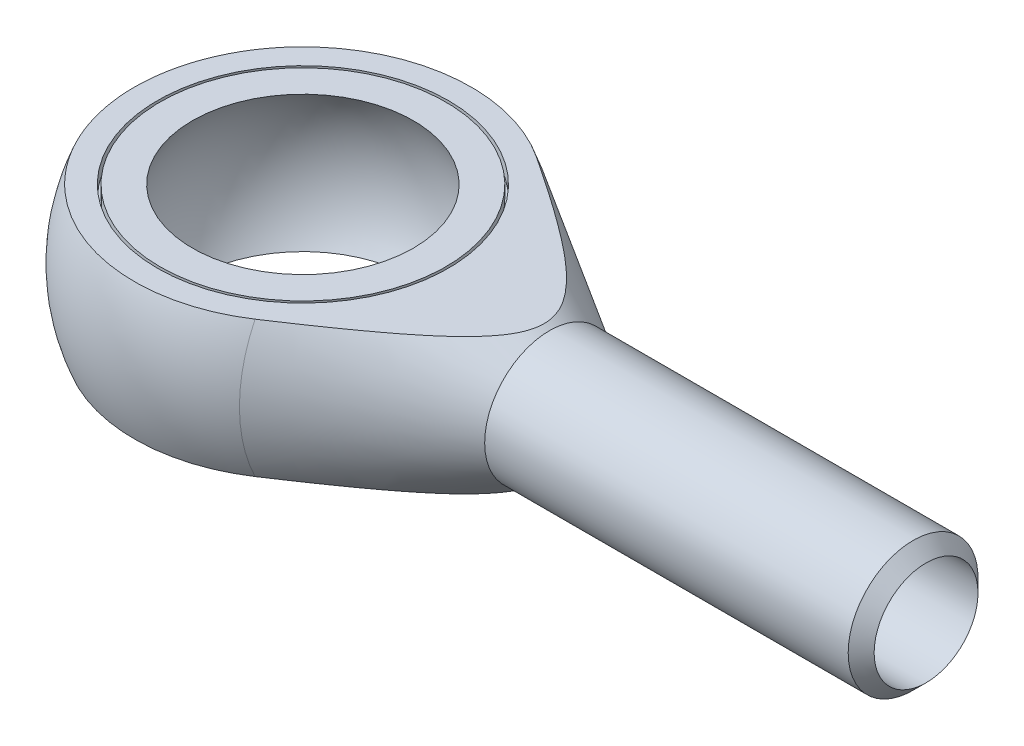
SolidWorks part; units mm, degrees
ref_plane "Front Plane" through (0, 0, 0) normal (0, 0, 1) x (1, 0, 0)
ref_plane "Top Plane" through (0, 0, 0) normal (0, 1, 0) x (1, 0, 0)
ref_plane "Right Plane" through (0, 0, 0) normal (1, 0, 0) x (0, 0, -1)
sketch "Sketch2" plane through (0, 0, 0) normal (0, 1, 0) x (1, 0, 0)
  line L0 (-39.4564, 0) -> (78.5867, 0) construction
  line L1 (7.148, 12.0377) -> (19, 5)
  line L2 (19, 5) -> (19, 0)
  line L3 (7.148, -12.0377) -> (19, -5) construction
  line L4 (-14, 0) -> (19, 0)
  arc A0 (-14, 0) -> (7.148, 12.0377) centre (0, 0) cw
  point P9 (19, 0)
  dimension "D2" = 14
  dimension "D1" = 10
  dimension "D3" = 19
revolve "Revolve2" add sketch "Sketch2" angle 360 about L0
sketch "Sketch3" plane through (0, 0, 0) normal (0, 0, 1) x (1, 0, 0)
  line L0 (-25.3278, 0) -> (34.1862, 0) construction
  line L1 (19, -5) -> (19, 5) construction
  line L2 (-14, 14) -> (19, 14)
  line L3 (-14, 14) -> (-14, 5.25)
  line L4 (-14, 5.25) -> (19, 5.25)
  line L5 (19, 14) -> (19, 5.25)
  line L6 (19, -14) -> (19, -5.25)
  line L7 (-14, -5.25) -> (19, -5.25)
  line L8 (-14, -14) -> (-14, -5.25)
  line L9 (-14, -14) -> (19, -14)
  arc A0 (7.148, 12.0377) -> (7.148, -12.0377) centre (0, 0) ccw construction
  dimension "D1" = 10.5
extrude "Cut-Extrude1" cut sketch "Sketch3" against normal through all and the other way through all
sketch "Sketch4" plane through (0, 0, 0) normal (0, 0, 1) x (1, 0, 0)
  line L0 (0, 13.976) -> (0, -14.0647) construction
  line L1 (0, 10) -> (0, -10)
  line L2 (-19.0477, 0) -> (26.0722, 0) construction
  line L3 (18.579, 5.25) -> (7.148, 5.25) construction
  line L4 (11, 5.25) -> (11.2, 5.25)
  line L5 (11, 5.25) -> (11, 4.25)
  line L6 (11, 4.25) -> (11.2, 4.25)
  line L7 (11.2, 5.25) -> (11.2, 4.25)
  line L8 (11.2, -5.25) -> (11.2, -4.25)
  line L9 (11, -4.25) -> (11.2, -4.25)
  line L10 (11, -5.25) -> (11, -4.25)
  line L11 (11, -5.25) -> (11.2, -5.25)
  arc A0 (0, -10) -> (0, 10) centre (0, 0) ccw
  dimension "D1" = 20
  dimension "D2" = 1
  dimension "D3" = 0.2
  dimension "D4" = 11
revolve "Cut-Revolve1" cut sketch "Sketch4" angle 360 about L0
sketch "Sketch5" plane through (19, 0, 0) normal (1, 0, 0) x (0, 0, -1)
  circle A1 centre (0, 0) radius 5
  circle A2 centre (0, 0) radius 5
  dimension "D1" = 0
extrude "Boss-Extrude1" add sketch "Sketch5" along normal blind 29
chamfer "Chamfer1" distance 1 angle 45 1 edges at (48, 0, -5)
ref_axis "Axis1" through (0, 5.775, 0) along (0, -1, 0)
sketch "Esquisse1" plane through (48, 0, 0) normal (1, 0, 0) x (0, 0, -1)
  circle A0 centre (0, 0) radius 4
extrude "Enlèv. mat.-Extru.1" cut sketch "Esquisse1" against normal blind 10
